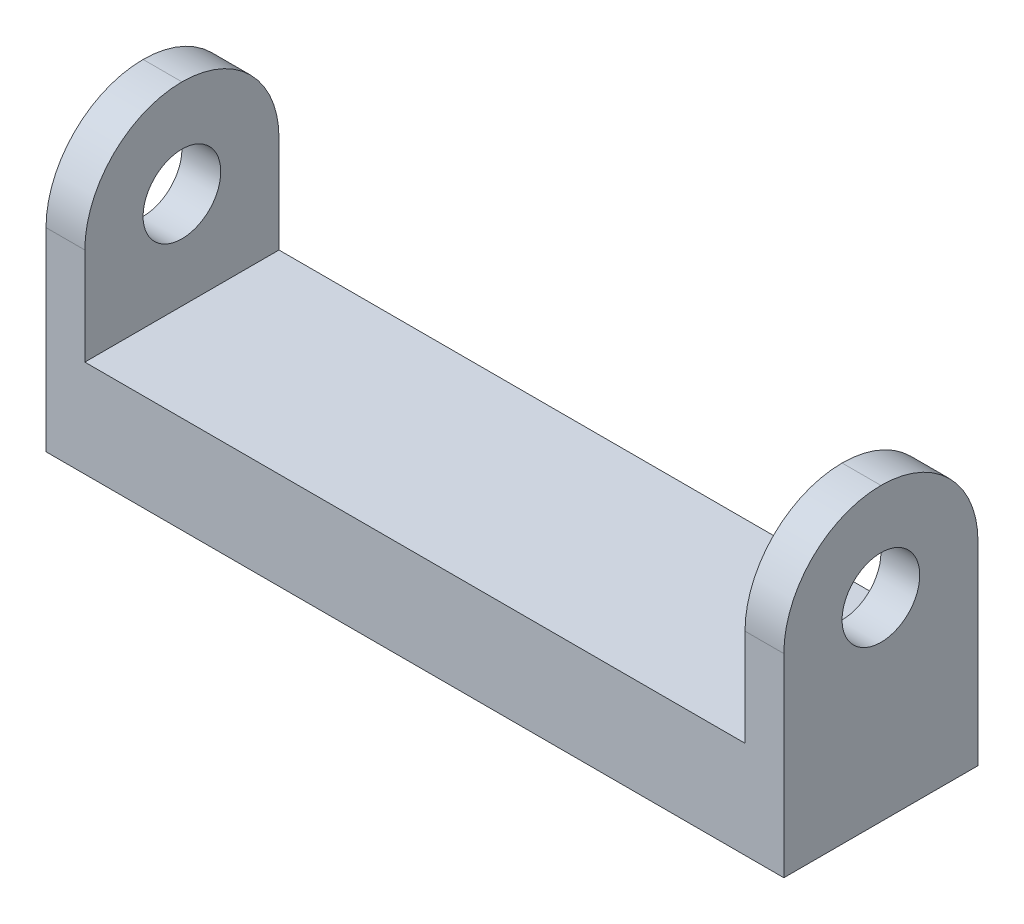
SolidWorks part; units mm, degrees
ref_plane "Front Plane" through (0, 0, 0) normal (0, 0, 1) x (1, 0, 0)
ref_plane "Top Plane" through (0, 0, 0) normal (0, 1, 0) x (1, 0, 0)
ref_plane "Right Plane" through (0, 0, 0) normal (1, 0, 0) x (0, 0, -1)
sketch "Sketch2" plane through (0, 0, 0) normal (0, 0, 1) x (1, 0, 0)
  line L0 (0, 0) -> (0, 150)
  line L1 (0, 150) -> (20, 150)
  line L2 (20, 150) -> (20, 50)
  line L3 (20, 50) -> (360, 50)
  line L4 (360, 50) -> (360, 150)
  line L5 (360, 150) -> (380, 150)
  line L6 (380, 150) -> (380, 0)
  line L7 (380, 0) -> (0, 0)
  dimension "D1" = 340
  dimension "D2" = 100
  dimension "D3" = 20
  dimension "D4" = 20
  dimension "D5" = 150
extrude "Boss-Extrude1" add sketch "Sketch2" along normal blind 100
fillet "Fillet4" radius 50 4 edges at (10, 150, 0) (10, 150, 100) (370, 150, 100) (370, 150, 0)
sketch "Sketch5" plane through (380, 0, 0) normal (1, 0, 0) x (0, 0, -1)
  circle A0 centre (-50, 100) radius 20
  arc A1 (0, 100) -> (-50, 150) centre (-50, 100) ccw construction
  dimension "D1" = 40
extrude "Cut-Extrude1" cut sketch "Sketch5" against normal through all
